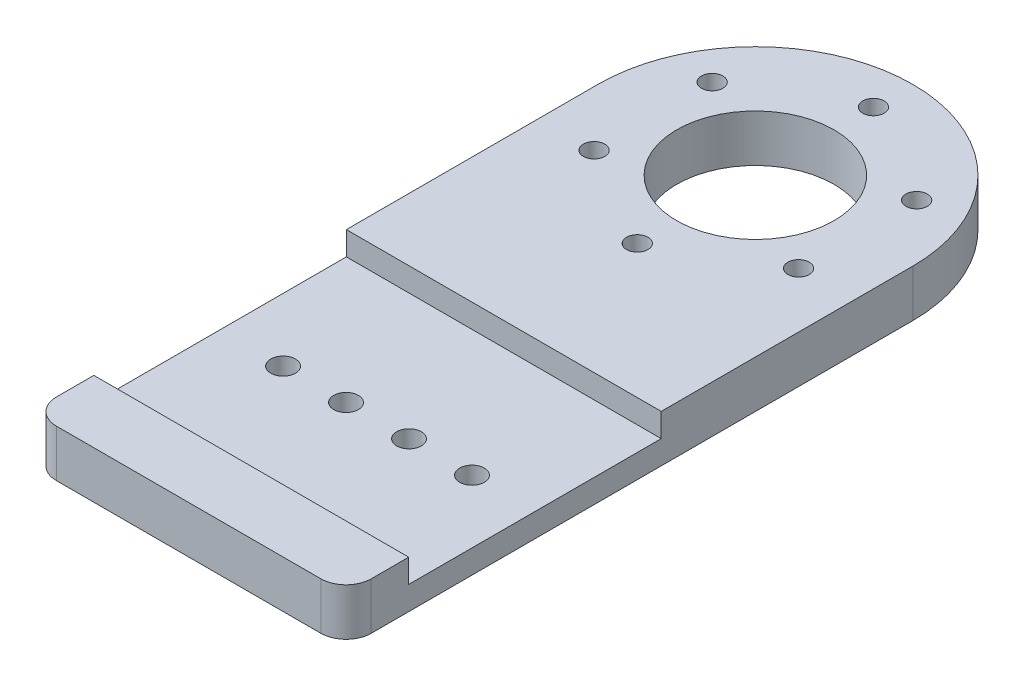
SolidWorks part; units mm, degrees
ref_plane "Front Plane" through (0, 0, 0) normal (0, 0, 1) x (1, 0, 0)
ref_plane "Top Plane" through (0, 0, 0) normal (0, 1, 0) x (1, 0, 0)
ref_plane "Right Plane" through (0, 0, 0) normal (1, 0, 0) x (0, 0, -1)
sketch "Sketch1" plane through (0, 0, 0) normal (0, 1, 0) x (1, 0, 0)
  line L0 (0, 12.6365) -> (63.5, 12.6365)
  line L2 (0, 114.3) -> (0, 0)
  line L3 (0, 0) -> (63.5, 0)
  line L4 (63.5, 114.3) -> (63.5, 0)
  line L5 (31.75, 114.3) -> (31.75, 146.05) construction
  line L7 (0, 63.5635) -> (63.5, 63.5635)
  circle A0 centre (31.75, 114.3) radius 15.875
  circle A1 centre (12.7, 38.1) radius 2.4892
  circle A2 centre (25.4, 38.1) radius 2.4892
  circle A3 centre (38.1, 38.1) radius 2.4892
  circle A4 centre (50.8, 38.1) radius 2.4892
  arc A8 (63.5, 114.3) -> (0, 114.3) centre (31.75, 114.3) ccw
  point P25 (63.5, -9.7091)
  dimension "D3" = 31.75
  dimension "D4" = 114.3
  dimension "D5" = 31.75
  dimension "D6" = 4.9784
  dimension "D7" = 12.7
  dimension "D8" = 25.4635
  dimension "D2" = 31.75
  dimension "D11" = 12.7
  dimension "D10" = 12.6365
  dimension "D12" = 63.5635
  dimension "D9" = 4
extrude "Boss-Extrude2" add sketch "Sketch1" along normal blind 9.525 contours L4 L0 L2 L3 | L2 L7 L4 A0 | A0 region at (31.75, 0, -6.3182) region at (1.041, 0, -88.9317)
extrude "Boss-Extrude3" add sketch "Sketch1<3>" along normal blind 4.7625 contours L7 L2 L0 L4 A4 A3 A2 A1 region at (31.75, 0, -38.1)
sketch "Sketch1<3>" plane through (0, 0, 0) normal (0, 1, 0) x (1, 0, 0) same geometry as "Sketch1"
sketch "Sketch2" plane through (0, 0, 0) normal (0, -1, 0) x (1, 0, 0)
  line L0 (31.75, -114.3) -> (11.1278, -102.3938) construction
  line L1 (31.75, -114.3) -> (31.75, -90.4875) construction
  circle A0 centre (11.1278, -102.3938) radius 2.159
  circle A4 centre (31.75, -114.3) radius 23.8125 construction
  circle A5 centre (31.75, -90.4875) radius 2.159
  circle A6 centre (52.3722, -102.3938) radius 2.159
  circle A7 centre (52.3722, -126.2063) radius 2.159
  circle A8 centre (31.75, -138.1125) radius 2.159
  circle A9 centre (11.1278, -126.2062) radius 2.159
  dimension "D1" = 4.318
  dimension "D3" = 60
  dimension "D4" = 47.625
  dimension "D2" = 6
extrude "Cut-Extrude1" cut sketch "Sketch2" against normal through all
sketch "Sketch3" plane through (0, 0, 0) normal (0, -1, 0) x (1, 0, 0)
  line L0 (-939.958, 0) -> (49060.042, 0) construction
  line L2 (63.5, -875.9909) -> (63.5, 49124.0091) construction
  point P3 (63.5, 0)
fillet "Fillet1" radius 5.08 2 edges at (0, 4.7625, 0) (63.5, 4.7625, 0)
